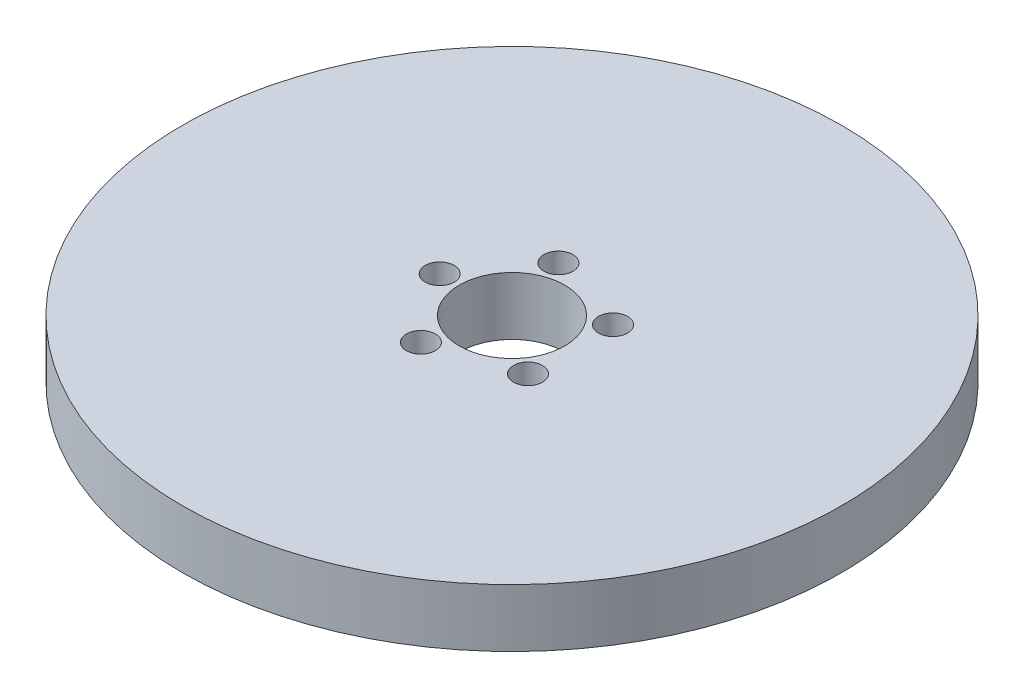
SolidWorks part; units mm, degrees
ref_plane "Front Plane" through (0, 0, 0) normal (0, 0, 1) x (1, 0, 0)
ref_plane "Top Plane" through (0, 0, 0) normal (0, 1, 0) x (1, 0, 0)
ref_plane "Right Plane" through (0, 0, 0) normal (1, 0, 0) x (0, 0, -1)
sketch "Sketch1" plane through (0, 0, 0) normal (0, 1, 0) x (1, 0, 0)
  circle A0 centre (0, 0) radius 62.5
  dimension "FLANGE_OD" = 125
extrude "Boss-Extrude1" add sketch "Sketch1" along normal blind 11
sketch "Sketch2" plane through (0, 0, 0) normal (0, 1, 0) x (1, 0, 0)
  circle A0 centre (0, 0) radius 10
  dimension "BORE_D" = 20
extrude "Cut-Extrude1" cut sketch "Sketch2" along normal through all
sketch "Sketch3" plane through (0, 11, 0) normal (0, 1, 0) x (1, 0, 0)
  circle A0 centre (0, 0) radius 13.7107 construction
  circle A1 centre (-13.7107, 0) radius 2.7512
  dimension "BOLT_D" = 5.5025
  dimension "BOLT_PCD" = 27.4215
extrude "Cut-Extrude2" cut sketch "Sketch3" against normal blind 10.7221
pattern_circular "CirPattern1" count 5 over 360 about axis through (0, 0, 0) along (0, 1, 0) of "Cut-Extrude2"
